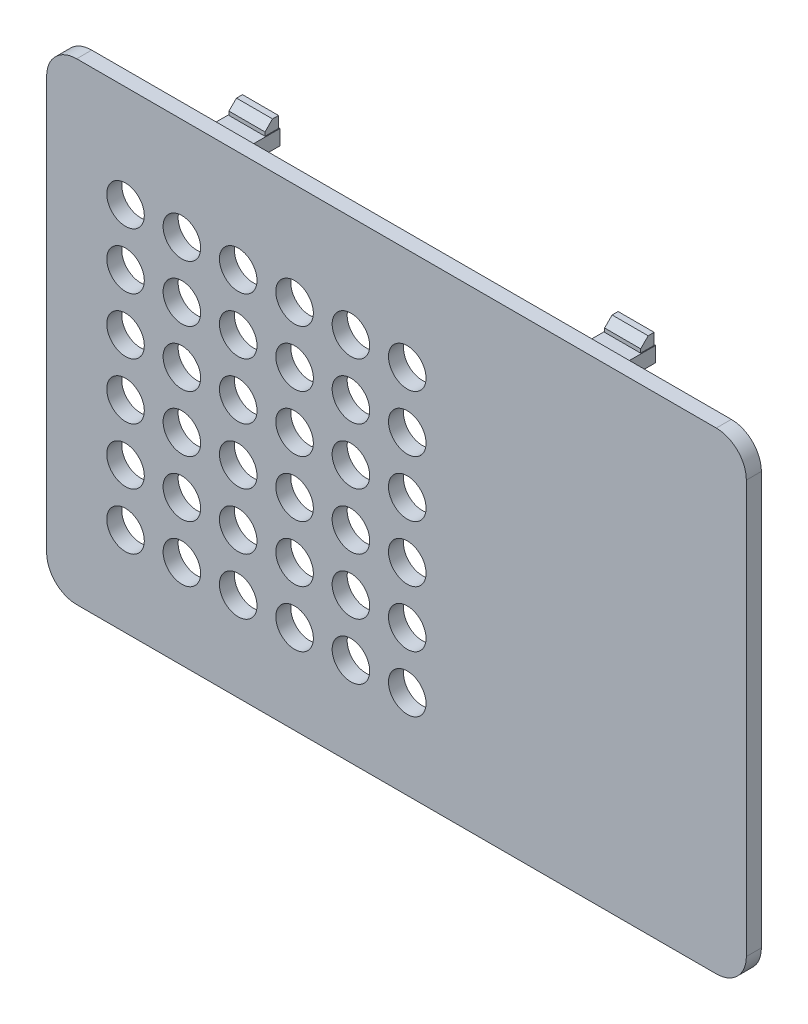
SolidWorks part; units mm, degrees
ref_plane "Front Plane" through (0, 0, 0) normal (0, 0, 1) x (1, 0, 0)
ref_plane "Top Plane" through (0, 0, 0) normal (0, 1, 0) x (1, 0, 0)
ref_plane "Right Plane" through (0, 0, 0) normal (1, 0, 0) x (0, 0, -1)
sketch "Sketch2" plane through (0, 0, 0) normal (0, 0, 1) x (1, 0, 0)
  line L0 (0, 0) -> (0, 50000) construction
  line L5 (0, 0) -> (50000, 0) construction
  line L6 (1.595, 55.4015) -> (-17.805, 55.4015) construction
  line L7 (42.565, 55.4015) -> (2.595, 55.4015) construction
  line L8 (45.065, -2.0185) -> (45.065, 49.9015) construction
  line L9 (46.565, -3.5185) -> (46.565, 51.4015) construction
  line L10 (-41.065, -6.0185) -> (41.065, -6.0185) construction
  line L11 (-42.565, -7.5185) -> (42.565, -7.5185) construction
  line L12 (41.065, 53.9015) -> (-41.065, 53.9015) construction
  line L13 (-45.065, 49.9015) -> (-45.065, -2.0185) construction
  line L14 (-46.565, 51.4015) -> (-46.565, -3.5185) construction
  line L15 (-18.805, 55.4015) -> (-42.565, 55.4015) construction
  line L16 (1.595, 55.4015) -> (-17.805, 55.4015)
  line L17 (42.565, 55.4015) -> (2.595, 55.4015)
  line L18 (45.065, -2.0185) -> (45.065, 49.9015)
  line L19 (46.565, -3.5185) -> (46.565, 51.4015)
  line L20 (-41.065, -6.0185) -> (41.065, -6.0185)
  line L21 (-42.565, -7.5185) -> (42.565, -7.5185)
  line L22 (41.065, 53.9015) -> (-41.065, 53.9015)
  line L23 (-45.065, 49.9015) -> (-45.065, -2.0185)
  line L24 (-46.565, 51.4015) -> (-46.565, -3.5185)
  line L25 (-18.805, 55.4015) -> (-42.565, 55.4015)
  line L26 (1.595, 55.4015) -> (2.595, 55.4015)
  line L27 (-18.805, 55.4015) -> (-17.805, 55.4015)
  line L28 (41.065, 51.9015) -> (-41.065, 51.9015)
  line L29 (-43.065, 49.9015) -> (-43.065, -2.0185)
  line L30 (-41.065, -4.0185) -> (41.065, -4.0185)
  line L31 (43.065, -2.0185) -> (43.065, 49.9015)
  arc A0 (45.065, 49.9015) -> (41.065, 53.9015) centre (41.065, 49.9015) ccw construction
  arc A1 (46.565, 51.4015) -> (42.565, 55.4015) centre (42.565, 51.4015) ccw construction
  arc A2 (41.065, -6.0185) -> (45.065, -2.0185) centre (41.065, -2.0185) ccw construction
  arc A3 (42.565, -7.5185) -> (46.565, -3.5185) centre (42.565, -3.5185) ccw construction
  arc A4 (-46.565, -3.5185) -> (-42.565, -7.5185) centre (-42.565, -3.5185) ccw construction
  arc A5 (-45.065, -2.0185) -> (-41.065, -6.0185) centre (-41.065, -2.0185) ccw construction
  arc A6 (-41.065, 53.9015) -> (-45.065, 49.9015) centre (-41.065, 49.9015) ccw construction
  arc A7 (-42.565, 55.4015) -> (-46.565, 51.4015) centre (-42.565, 51.4015) ccw construction
  arc A8 (45.065, 49.9015) -> (41.065, 53.9015) centre (41.065, 49.9015) ccw
  arc A9 (46.565, 51.4015) -> (42.565, 55.4015) centre (42.565, 51.4015) ccw
  arc A10 (41.065, -6.0185) -> (45.065, -2.0185) centre (41.065, -2.0185) ccw
  arc A11 (42.565, -7.5185) -> (46.565, -3.5185) centre (42.565, -3.5185) ccw
  arc A12 (-46.565, -3.5185) -> (-42.565, -7.5185) centre (-42.565, -3.5185) ccw
  arc A13 (-45.065, -2.0185) -> (-41.065, -6.0185) centre (-41.065, -2.0185) ccw
  arc A14 (-41.065, 53.9015) -> (-45.065, 49.9015) centre (-41.065, 49.9015) ccw
  arc A15 (-42.565, 55.4015) -> (-46.565, 51.4015) centre (-42.565, 51.4015) ccw
  arc A16 (43.065, 49.9015) -> (41.065, 51.9015) centre (41.065, 49.9015) ccw
  arc A17 (-41.065, 51.9015) -> (-43.065, 49.9015) centre (-41.065, 49.9015) ccw
  arc A18 (-43.065, -2.0185) -> (-41.065, -4.0185) centre (-41.065, -2.0185) ccw
  arc A19 (41.065, -4.0185) -> (43.065, -2.0185) centre (41.065, -2.0185) ccw
  dimension "D1" = 2
extrude "Boss-Extrude2" add sketch "Sketch2" along normal blind 2 contours L30 A19 L31 A16 L28 A17 L29 A18 | L22 A14 L23 A13 L20 A10 L18 A8 A19 L30 A18 L29 A17 L28 A16 L31 | L25 A15 L24 A12 L21 A11 L19 A9 L17 L26 L16 L27 A14 L22 A8 L18 A10 L20 A13 L23 region at (2.095, 54.2776, 0) region at (43.1281, -4.0816, 0) region at (0, 23.9415, 0)
extrude "Boss-Extrude3" add sketch "Sketch2<3>" against normal blind 2 contours L22 A14 L23 A13 L20 A10 L18 A8 A19 L30 A18 L29 A17 L28 A16 L31 region at (43.1281, -4.0816, 0)
sketch "Sketch2<3>" plane through (0, 0, 0) normal (0, 0, 1) x (1, 0, 0) same geometry as "Sketch2"
chamfer "Chamfer1" distance 1 distance2 2 8 edges at (0, 53.9015, -2) (-43.8934, 52.73, -2) (43.8934, 52.73, -2) (-45.065, 23.9415, -2) (45.065, 23.9415, -2) (-43.8934, -4.8469, -2) (43.8934, -4.8469, -2) (0, -6.0185, -2) first distance on face at (0, 23.9415, -2)
sketch "Sketch3" plane through (0, 0, 0) normal (0, 0, -1) x (-1, 0, 0)
  line L0 (27.5, 53.9015) -> (22.5, 53.9015) construction
  line L1 (-22.5, 53.9015) -> (-27.5, 53.9015) construction
  line L2 (-22.5, -6.0185) -> (-27.5, -6.0185) construction
  line L3 (27.5, -6.0185) -> (22.5, -6.0185) construction
  line L4 (27.5, 53.9015) -> (22.5, 53.9015)
  line L5 (-22.5, 53.9015) -> (-27.5, 53.9015)
  line L6 (-22.5, -6.0185) -> (-27.5, -6.0185)
  line L7 (27.5, -6.0185) -> (22.5, -6.0185)
  line L9 (27.5, 53.9015) -> (22.5, 53.9015)
  line L10 (27.5, 53.9015) -> (27.5, 51.9015)
  line L11 (27.5, 51.9015) -> (22.5, 51.9015)
  line L12 (22.5, 53.9015) -> (22.5, 51.9015)
  line L13 (-22.5, 53.9015) -> (-27.5, 53.9015)
  line L14 (-22.5, 53.9015) -> (-22.5, 51.9015)
  line L15 (-22.5, 51.9015) -> (-27.5, 51.9015)
  line L16 (-27.5, 53.9015) -> (-27.5, 51.9015)
  line L17 (27.5, -6.0185) -> (22.5, -6.0185)
  line L18 (27.5, -6.0185) -> (27.5, -4.0185)
  line L19 (27.5, -4.0185) -> (22.5, -4.0185)
  line L20 (22.5, -6.0185) -> (22.5, -4.0185)
  line L21 (-22.5, -6.0185) -> (-27.5, -6.0185)
  line L22 (-22.5, -6.0185) -> (-22.5, -4.0185)
  line L23 (-22.5, -4.0185) -> (-27.5, -4.0185)
  line L24 (-27.5, -6.0185) -> (-27.5, -4.0185)
  line M6 (-41.065, -4.0185) -> (41.065, -4.0185)
  line M10 (41.065, 51.9015) -> (-41.065, 51.9015)
  dimension "D1" = 2
  dimension "D2" = 2
  dimension "D3" = 2
  dimension "D4" = 2
extrude "Boss-Extrude4" add sketch "Sketch3" along normal up to surface (5 mm away) contours L4 L12 L10 M10 | L20 L7 L18 M6 | L24 L6 L22 M6 | L5 L16 L14 M10 region at (-25, 52.9015, 0) region at (25, 52.9015, 0) region at (-25, -5.0185, 0) region at (25, -5.0185, 0)
sketch "Sketch4" plane through (0, 53.9015, 0) normal (0, 1, 0) x (1, 0, 0)
  line L85 (27.4, 4.9) -> (22.6, 4.9)
  line L86 (27.4, 3.1) -> (27.4, 4.9)
  line L87 (22.6, 3.1) -> (27.4, 3.1)
  line L88 (22.6, 4.9) -> (22.6, 3.1)
  line L89 (27.4, 4.9) -> (22.6, 4.9)
  line L90 (27.4, 3.1) -> (27.4, 4.9)
  line L91 (22.6, 3.1) -> (27.4, 3.1)
  line L92 (22.6, 4.9) -> (22.6, 3.1)
  line L103 (-22.6, 3.1) -> (-22.6, 4.9)
  line L104 (-27.4, 3.1) -> (-22.6, 3.1)
  line L105 (-27.4, 4.9) -> (-27.4, 3.1)
  line L106 (-22.6, 4.9) -> (-27.4, 4.9)
  line L107 (-22.6, 3.1) -> (-22.6, 4.9)
  line L108 (-27.4, 3.1) -> (-22.6, 3.1)
  line L109 (-27.4, 4.9) -> (-27.4, 3.1)
  line L110 (-22.6, 4.9) -> (-27.4, 4.9)
  dimension "D1" = 0.1
  dimension "D2" = 0.1
extrude "Boss-Extrude5" add sketch "Sketch4" along normal up to surface (1.5 mm away)
extrude "Boss-Extrude6" add sketch "Sketch4<2>" against normal up to surface (1.5 mm away) from surface starting at face at (-25, -6.0185, -2.5)
sketch "Sketch4<2>" plane through (0, 53.9015, 0) normal (0, 1, 0) x (1, 0, 0) same geometry as "Sketch4"
chamfer "Chamfer2" distance 1 angle 45 4 edges at (25, 55.4015, -3.1) (-25, 55.4015, -3.1) (25, -7.5185, -3.1) (-25, -7.5185, -3.1)
sketch "Sketch5" plane through (0, 0, 2) normal (0, 0, 1) x (1, 0, 0)
  line L0 (-39.065, 44.3315) -> (-39.065, 4.3315) construction
  line L1 (-39.065, 4.3315) -> (3.935, 4.3315) construction
  line L2 (3.935, 4.3315) -> (3.935, 44.3315) construction
  line L3 (3.935, 44.3315) -> (-39.065, 44.3315) construction
  line L4 (42.565, 55.4015) -> (-42.565, 55.4015)
  line L5 (-46.565, 51.4015) -> (-46.565, -3.5185)
  line L6 (-42.565, -7.5185) -> (42.565, -7.5185)
  line L7 (46.565, -3.5185) -> (46.565, 51.4015)
  line L8 (42.565, 55.4015) -> (-42.565, 55.4015)
  line L9 (-46.565, 51.4015) -> (-46.565, -3.5185)
  line L10 (-42.565, -7.5185) -> (42.565, -7.5185)
  line L11 (46.565, -3.5185) -> (46.565, 51.4015)
  line L12 (-39.065, 44.3315) -> (-39.065, 4.3315) construction
  line L13 (-39.065, 4.3315) -> (3.935, 4.3315) construction
  line L14 (3.935, 4.3315) -> (3.935, 44.3315) construction
  line L15 (3.935, 44.3315) -> (-39.065, 44.3315) construction
  circle A0 centre (1.435, 41.8315) radius 2.5
  circle A1 centre (-6.065, 41.8315) radius 2.5
  circle A2 centre (-13.565, 41.8315) radius 2.5
  circle A3 centre (-21.065, 41.8315) radius 2.5
  arc A4 (-42.565, 55.4015) -> (-46.565, 51.4015) centre (-42.565, 51.4015) ccw
  arc A5 (-46.565, -3.5185) -> (-42.565, -7.5185) centre (-42.565, -3.5185) ccw
  arc A6 (42.565, -7.5185) -> (46.565, -3.5185) centre (42.565, -3.5185) ccw
  arc A7 (46.565, 51.4015) -> (42.565, 55.4015) centre (42.565, 51.4015) ccw
  arc A8 (-42.565, 55.4015) -> (-46.565, 51.4015) centre (-42.565, 51.4015) ccw
  arc A9 (-46.565, -3.5185) -> (-42.565, -7.5185) centre (-42.565, -3.5185) ccw
  arc A10 (42.565, -7.5185) -> (46.565, -3.5185) centre (42.565, -3.5185) ccw
  arc A11 (46.565, 51.4015) -> (42.565, 55.4015) centre (42.565, 51.4015) ccw
  circle A12 centre (-28.565, 41.8315) radius 2.5
  circle A13 centre (-36.065, 41.8315) radius 2.5
  circle A14 centre (-6.065, 34.3315) radius 2.5
  circle A15 centre (-13.565, 34.3315) radius 2.5
  circle A16 centre (-21.065, 34.3315) radius 2.5
  circle A17 centre (-28.565, 34.3315) radius 2.5
  circle A18 centre (-36.065, 34.3315) radius 2.5
  circle A19 centre (-6.065, 26.8315) radius 2.5
  circle A20 centre (-13.565, 26.8315) radius 2.5
  circle A21 centre (-21.065, 26.8315) radius 2.5
  circle A22 centre (-28.565, 26.8315) radius 2.5
  circle A23 centre (-36.065, 26.8315) radius 2.5
  circle A24 centre (-6.065, 19.3315) radius 2.5
  circle A25 centre (-13.565, 19.3315) radius 2.5
  circle A26 centre (-21.065, 19.3315) radius 2.5
  circle A27 centre (-28.565, 19.3315) radius 2.5
  circle A28 centre (-36.065, 19.3315) radius 2.5
  circle A29 centre (-6.065, 11.8315) radius 2.5
  circle A30 centre (-13.565, 11.8315) radius 2.5
  circle A31 centre (-21.065, 11.8315) radius 2.5
  circle A32 centre (-28.565, 11.8315) radius 2.5
  circle A33 centre (-36.065, 11.8315) radius 2.5
  circle A34 centre (-6.065, 4.3315) radius 2.5
  circle A35 centre (-13.565, 4.3315) radius 2.5
  circle A36 centre (-21.065, 4.3315) radius 2.5
  circle A37 centre (-28.565, 4.3315) radius 2.5
  circle A38 centre (-36.065, 4.3315) radius 2.5
  circle A39 centre (1.435, 34.3315) radius 2.5
  circle A40 centre (1.435, 26.8315) radius 2.5
  circle A41 centre (1.435, 19.3315) radius 2.5
  circle A42 centre (1.435, 11.8315) radius 2.5
  circle A43 centre (1.435, 4.3315) radius 2.5
  dimension "D2" = 5
  dimension "D3" = 6
  dimension "D1" = 0
  dimension "D4" = 6
extrude "Cut-Extrude1" cut sketch "Sketch5" against normal up to next (2 mm away) contours A0 | A1 | A2 | A3 | A12 | A13 | A18 | A17 | A16 | A15 | A14 | A39 | A40 | A19 | A20 | A21 | A22 | A23 | A28 | A27 | A26 | A25 | A24 | A41 | A42 | A29 | A30 | A31 | A32 | A33 | A38 | A37 | A36 | A35 | A34 | A43 region at (1.435, 41.8315, 2) region at (-6.065, 41.8315, 2) region at (-13.565, 41.8315, 2) region at (-21.065, 41.8315, 2) region at (-28.565, 41.8315, 2) region at (-36.065, 41.8315, 2) region at (-6.065, 34.3315, 2) region at (-13.565, 34.3315, 2) region at (-21.065, 34.3315, 2) region at (-28.565, 34.3315, 2) region at (-36.065, 34.3315, 2) region at (-6.065, 26.8315, 2) region at (-13.565, 26.8315, 2) region at (-21.065, 26.8315, 2) region at (-28.565, 26.8315, 2) region at (-36.065, 26.8315, 2) region at (-6.065, 19.3315, 2) region at (-13.565, 19.3315, 2) region at (-21.065, 19.3315, 2) region at (-28.565, 19.3315, 2) region at (-36.065, 19.3315, 2) region at (-6.065, 11.8315, 2) region at (-13.565, 11.8315, 2) region at (-21.065, 11.8315, 2) region at (-28.565, 11.8315, 2) region at (-36.065, 11.8315, 2) region at (-6.065, 4.3315, 2) region at (-13.565, 4.3315, 2) region at (-21.065, 4.3315, 2) region at (-28.565, 4.3315, 2) region at (-36.065, 4.3315, 2) region at (1.435, 34.3315, 2) region at (1.435, 26.8315, 2) region at (1.435, 19.3315, 2) region at (1.435, 11.8315, 2) region at (1.435, 4.3315, 2)
sketch "Sketch6" plane through (0, 0, 2) normal (0, 0, 1) x (1, 0, 0)
  line L0 (-42.565, -7.5185) -> (42.565, -7.5185) construction
  circle A0 centre (0, 23.9415) radius 12.1901 construction
  point P4 (0, -7.5185)
